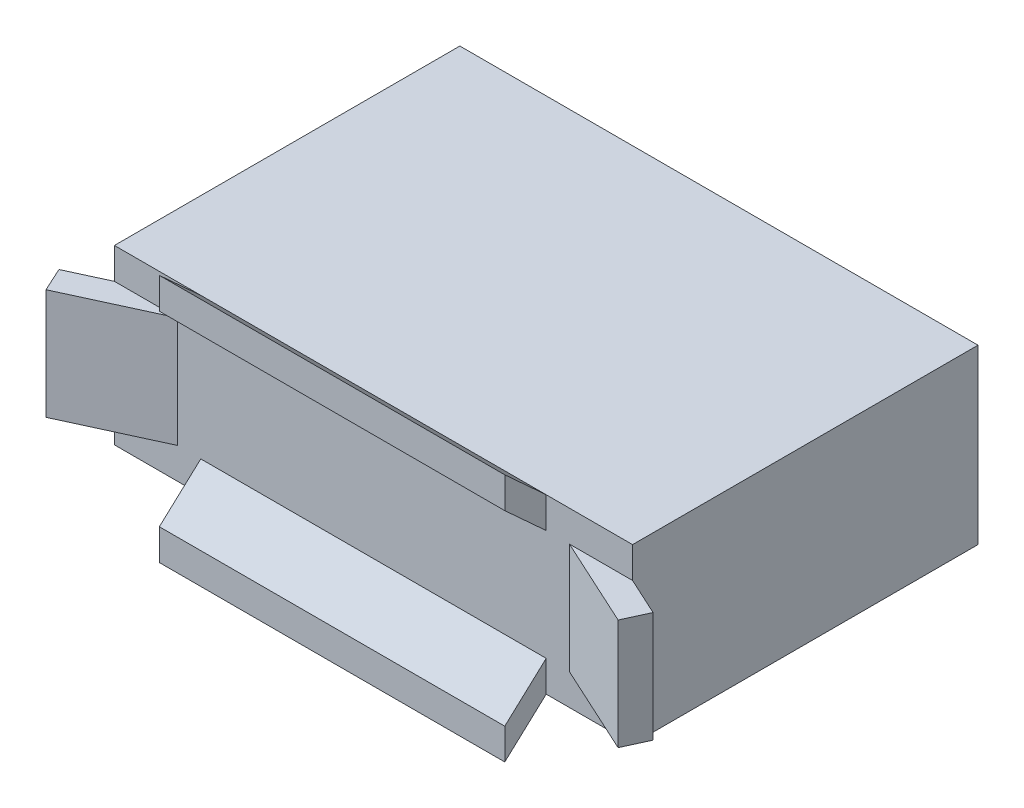
SolidWorks part; units mm, degrees
ref_plane "Front Plane" through (0, 0, 0) normal (0, 0, 1) x (1, 0, 0)
ref_plane "Top Plane" through (0, 0, 0) normal (0, 1, 0) x (1, 0, 0)
ref_plane "Right Plane" through (0, 0, 0) normal (1, 0, 0) x (0, 0, -1)
sketch "Sketch1" plane through (0, 0, 0) normal (0, 1, 0) x (1, 0, 0)
  line L1 (-3.75, -2.5) -> (3.75, -2.5)
  line L2 (-3.75, -2.5) -> (-3.75, 2.5)
  line L3 (-3.75, 2.5) -> (3.75, 2.5)
  line L4 (3.75, -2.5) -> (3.75, 2.5)
  line L5 (-3.75, -2.5) -> (3.75, 2.5) construction
  line L6 (-3.75, 2.5) -> (3.75, -2.5) construction
  point P0 (0, 0)
  dimension "D1" = 7.5
  dimension "D2" = 5
extrude "Boss-Extrude1" add sketch "Sketch1" along normal blind 1.25 and the other way blind 1.25
sketch "Sketch3" plane through (0, 0, 0) normal (0, 1, 0) x (1, 0, 0)
  line L0 (-3.75, -2.5) -> (-4.3, -2.7529)
  line L1 (-4.3, -2.7529) -> (-4.1404, -3.1)
  line L2 (-4.1404, -3.1) -> (-2.8358, -2.5)
  line L3 (-3.75, -2.5) -> (3.75, -2.5) construction
  line L4 (-3.75, -2.5) -> (-2.8358, -2.5)
  line L5 (0, 0) -> (0, -2.5) construction
  line L6 (3.75, -2.5) -> (2.8358, -2.5)
  line L7 (4.1404, -3.1) -> (2.8358, -2.5)
  line L8 (4.3, -2.7529) -> (4.1404, -3.1)
  line L9 (3.75, -2.5) -> (4.3, -2.7529)
  dimension "D1" = 0.6
  dimension "D2" = 0.55
extrude "Boss-Extrude2" add sketch "Sketch3" along normal blind 0.8 and the other way blind 0.8
sketch "Sketch5" plane through (0, 0, 0) normal (1, 0, 0) x (0, 0, -1)
  line L0 (-2.5, 1.25) -> (-3.1, 1.8)
  line L1 (-3.1, 1.8) -> (-3.1, 1.3508)
  line L2 (-3.1, 1.3508) -> (-2.5, 0.8008)
  line L3 (-2.5, 0.8) -> (-2.5, 1.25) construction
  line L4 (-2.5, 0.8008) -> (-2.5, 1.25)
  line L5 (0, 0) -> (-2.5, 0) construction
  line L6 (-2.5, -0.8) -> (-2.5, 0.8) construction
  line L7 (-2.5, -0.8008) -> (-2.5, -1.25)
  line L8 (-3.1, -1.3508) -> (-2.5, -0.8008)
  line L9 (-3.1, -1.8) -> (-3.1, -1.3508)
  line L10 (-2.5, -1.25) -> (-3.1, -1.8)
  dimension "D1" = 0.55
  dimension "D2" = 0.6
extrude "Boss-Extrude3" add sketch "Sketch5" along normal blind 2.5 and the other way blind 2.5
